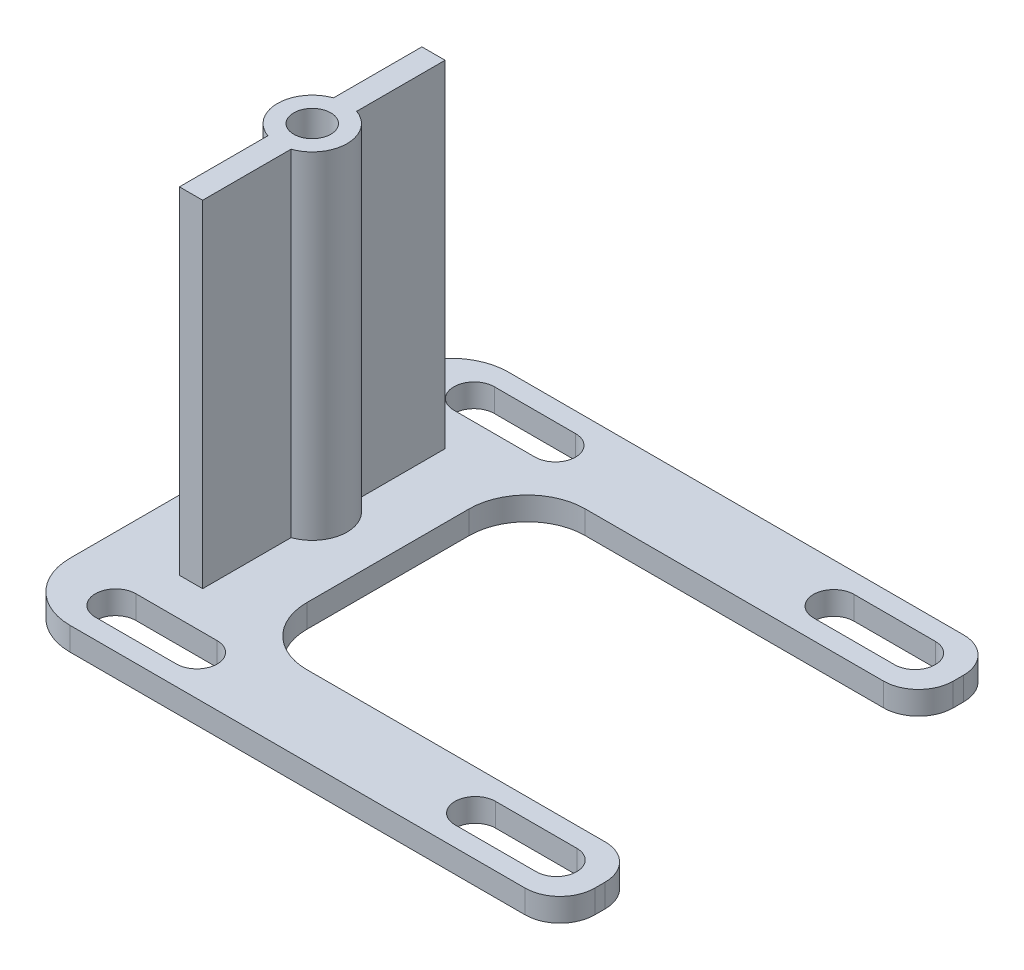
SolidWorks part; units mm, degrees
ref_plane "Front Plane" through (0, 0, 0) normal (0, 0, 1) x (1, 0, 0)
ref_plane "Top Plane" through (0, 0, 0) normal (0, 1, 0) x (1, 0, 0)
ref_plane "Right Plane" through (0, 0, 0) normal (1, 0, 0) x (0, 0, -1)
sketch "Sketch1" plane through (0, 0, 0) normal (0, 1, 0) x (1, 0, 0)
  line L0 (47.2433, 30.9) -> (47.2433, 37.8)
  line L1 (47.2433, 6.9) -> (13.5188, 6.9)
  line L3 (47.2433, 30.9) -> (13.5188, 30.9)
  line L4 (13.5188, 6.9) -> (13.5188, 30.9)
  line L5 (5.4933, 34.35) -> (12.4933, 34.35) construction
  line L6 (5.4933, 36.1) -> (12.4933, 36.1)
  line L7 (47.2433, 0) -> (0, 0)
  line L9 (47.2433, 37.8) -> (0, 37.8)
  line L10 (0, 0) -> (0, 37.8)
  line L11 (5.4933, 32.6) -> (12.4933, 32.6)
  line L12 (36.4933, 34.35) -> (43.4933, 34.35) construction
  line L13 (47.2433, 6.9) -> (47.2433, 0)
  line L14 (36.4933, 36.1) -> (43.4933, 36.1)
  line L15 (36.4933, 32.6) -> (43.4933, 32.6)
  line L16 (5.4933, 3.45) -> (12.4933, 3.45) construction
  line L17 (5.4933, 5.2) -> (12.4933, 5.2)
  line L18 (5.4933, 1.7) -> (12.4933, 1.7)
  line L19 (36.4933, 3.45) -> (43.4933, 3.45) construction
  line L20 (36.4933, 5.2) -> (43.4933, 5.2)
  line L21 (36.4933, 1.7) -> (43.4933, 1.7)
  line L22 (8.9933, 34.35) -> (39.9933, 3.45) construction
  line L23 (39.9933, 34.35) -> (8.9933, 3.45) construction
  arc A0 (5.4933, 36.1) -> (5.4933, 32.6) centre (5.4933, 34.35) ccw
  arc A1 (12.4933, 32.6) -> (12.4933, 36.1) centre (12.4933, 34.35) ccw
  arc A2 (36.4933, 36.1) -> (36.4933, 32.6) centre (36.4933, 34.35) ccw
  arc A3 (43.4933, 32.6) -> (43.4933, 36.1) centre (43.4933, 34.35) ccw
  arc A4 (5.4933, 5.2) -> (5.4933, 1.7) centre (5.4933, 3.45) ccw
  arc A5 (12.4933, 1.7) -> (12.4933, 5.2) centre (12.4933, 3.45) ccw
  arc A6 (36.4933, 5.2) -> (36.4933, 1.7) centre (36.4933, 3.45) ccw
  arc A7 (43.4933, 1.7) -> (43.4933, 5.2) centre (43.4933, 3.45) ccw
  point P0 (0, 0)
  point P6 (0, 0)
  point P8 (8.9933, 34.35)
  point P18 (39.9933, 34.35)
  point P25 (8.9933, 3.45)
  point P32 (39.9933, 3.45)
  point P39 (47.2433, 34.35)
  point P40 (47.2433, 3.45)
  point P43 (45.2433, 34.35)
  dimension "D3" = 1.75
  dimension "D1" = 6.9
  dimension "D2" = 7
  dimension "D4" = 38
  dimension "D5" = 2
  dimension "D6" = 30.9
extrude "Boss-Extrude1" add sketch "Sketch1" along normal blind 2
fillet "Fillet1" radius 5 4 edges at (0, 1, -37.8) (0, 1, 0) (13.5188, 1, -6.9) (13.5188, 1, -30.9)
fillet "Fillet2" radius 3 4 edges at (47.2433, 1, -6.9) (47.2433, 1, 0) (47.2433, 1, -30.9) (47.2433, 1, -37.8)
sketch "Sketch2" plane through (0, 2, 0) normal (0, 1, 0) x (1, 0, 0)
  line L0 (0, 32.8) -> (0, 5) construction
  line L2 (12.4933, 6.9) -> (36.4933, 6.9) construction
  line L3 (12.4933, 6.9) -> (12.4933, 30.9) construction
  line L4 (12.4933, 30.9) -> (36.4933, 30.9) construction
  line L5 (36.4933, 6.9) -> (36.4933, 30.9) construction
  line L6 (12.4933, 6.9) -> (36.4933, 30.9) construction
  line L7 (12.4933, 30.9) -> (36.4933, 6.9) construction
  line L9 (5.9933, 21.7284) -> (5.9933, 29.35)
  line L10 (5.9933, 29.35) -> (7.9933, 29.35)
  line L11 (7.9933, 21.7284) -> (7.9933, 29.35)
  line L13 (5.9933, 16.0716) -> (5.9933, 8.45)
  line L14 (5.9933, 8.45) -> (7.9933, 8.45)
  line L15 (7.9933, 16.0716) -> (7.9933, 8.45)
  arc A0 (5.9933, 21.7284) -> (5.9933, 16.0716) centre (6.9933, 18.9) ccw
  circle A1 centre (6.9933, 18.9) radius 1.6
  arc A2 (5.4933, 36.1) -> (5.4933, 32.6) centre (5.4933, 34.35) ccw construction
  arc A3 (5.4933, 5.2) -> (5.4933, 1.7) centre (5.4933, 3.45) ccw construction
  arc A4 (7.9933, 16.0716) -> (7.9933, 21.7284) centre (6.9933, 18.9) ccw
  point P6 (0, 18.9)
  point P7 (24.4933, 18.9)
  point P20 (0, 0)
  point P24 (3.7433, 34.35)
  point P28 (3.7433, 3.45)
  point P29 (0, 0)
  point P30 (5.8697, 29.35)
  dimension "D1" = 3.2
  dimension "D2" = 6
  dimension "D3" = 24
  dimension "D4" = 24
  dimension "D5" = 17.5
  dimension "D6" = 5
  dimension "D7" = 5
  dimension "D8" = 2
  dimension "D9" = 2
extrude "Boss-Extrude2" add sketch "Sketch2" along normal blind 29
